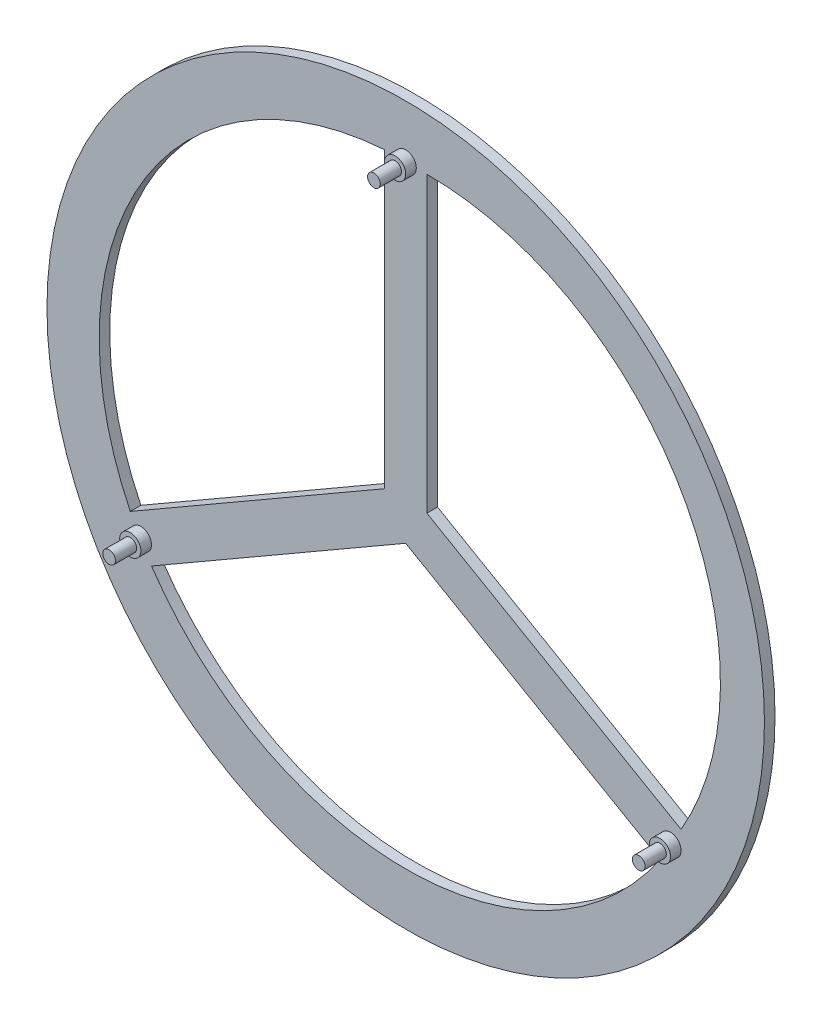
SolidWorks part; units mm, degrees
note: The reader was unsure of these and kept them because the rebuilt part matched: shared geometry of "Sketch1<4>", "Sketch1<5>".
ref_plane "Front Plane" through (0, 0, 0) normal (0, 0, 1) x (1, 0, 0)
ref_plane "Top Plane" through (0, 0, 0) normal (0, 1, 0) x (1, 0, 0)
ref_plane "Right Plane" through (0, 0, 0) normal (1, 0, 0) x (0, 0, -1)
sketch "Sketch1" plane through (0, 0, 0) normal (0, 0, 1) x (1, 0, 0)
  line L2 (-21.9945, 277.2204) -> (228.0055, 132.8828) construction
  line L4 (-21.9945, 277.2204) -> (-21.9945, 565.8955) construction
  line L9 (-21.9945, 277.2204) -> (-271.9945, 132.8828) construction
  line L10 (-41.9945, 288.7674) -> (-281.9945, 150.2034)
  line L11 (-41.9945, 288.7674) -> (-41.9945, 565.8955)
  line L12 (-1.9945, 288.7674) -> (238.0055, 150.2034)
  line L13 (-1.9945, 288.7674) -> (-1.9945, 565.8955)
  line L14 (-21.9945, 254.1264) -> (-261.9945, 115.5623)
  line L15 (-21.9945, 254.1264) -> (218.0055, 115.5623)
  circle A0 centre (228.0055, 132.8828) radius 6
  circle A1 centre (-271.9945, 132.8828) radius 6
  circle A2 centre (-21.9945, 565.8955) radius 6
  circle A3 centre (-21.9945, 277.2204) radius 288.6751 construction
  circle A4 centre (-21.9945, 277.2204) radius 338.6751
  arc A5 (-281.9945, 150.2034) -> (-41.7313, 565.9137) centre (-21.9945, 277.2204) cw
  arc A6 (238.0055, 150.2034) -> (-1.9945, 565.8955) centre (-1.9945, 288.7674) ccw
  arc A7 (-261.9945, 115.5623) -> (218.0055, 115.5623) centre (-21.9945, 277.2204) ccw
  circle A8 centre (-271.9945, 132.8828) radius 10
  circle A9 centre (-21.9945, 565.8955) radius 10
  circle A10 centre (228.0055, 132.8828) radius 10
  dimension "D1" = 12
  dimension "D3" = 12
  dimension "D6" = 12
  dimension "D4" = 500
  dimension "D5" = 50
  dimension "D8" = 20
  dimension "D2" = 20
  dimension "D7" = 20
  dimension "D9" = 4
extrude "Boss-Extrude1" add sketch "Sketch1" along normal blind 10
extrude "Boss-Extrude2" add sketch "Sketch1<4>" along normal blind 40 contours A0 | A2 | A1
sketch "Sketch1<4>" plane through (0, 0, 0) normal (0, 0, 1) x (1, 0, 0) same geometry as "Sketch1"
extrude "Boss-Extrude3" add sketch "Sketch1<5>" along direction (0, 0, 1) on the side of the normal blind 20 contours A9 | A10 | A8
sketch "Sketch1<5>" plane through (0, 0, 0) normal (0, 0, 1) x (1, 0, 0) same geometry as "Sketch1"
equation "\"HOLE_DIAM\"= 12"
equation "\"D1@Sketch1\"=\"HOLE_DIAM\""
equation "\"D3@Sketch1\"=\"HOLE_DIAM\""
equation "\"D6@Sketch1\"=\"HOLE_DIAM\""
